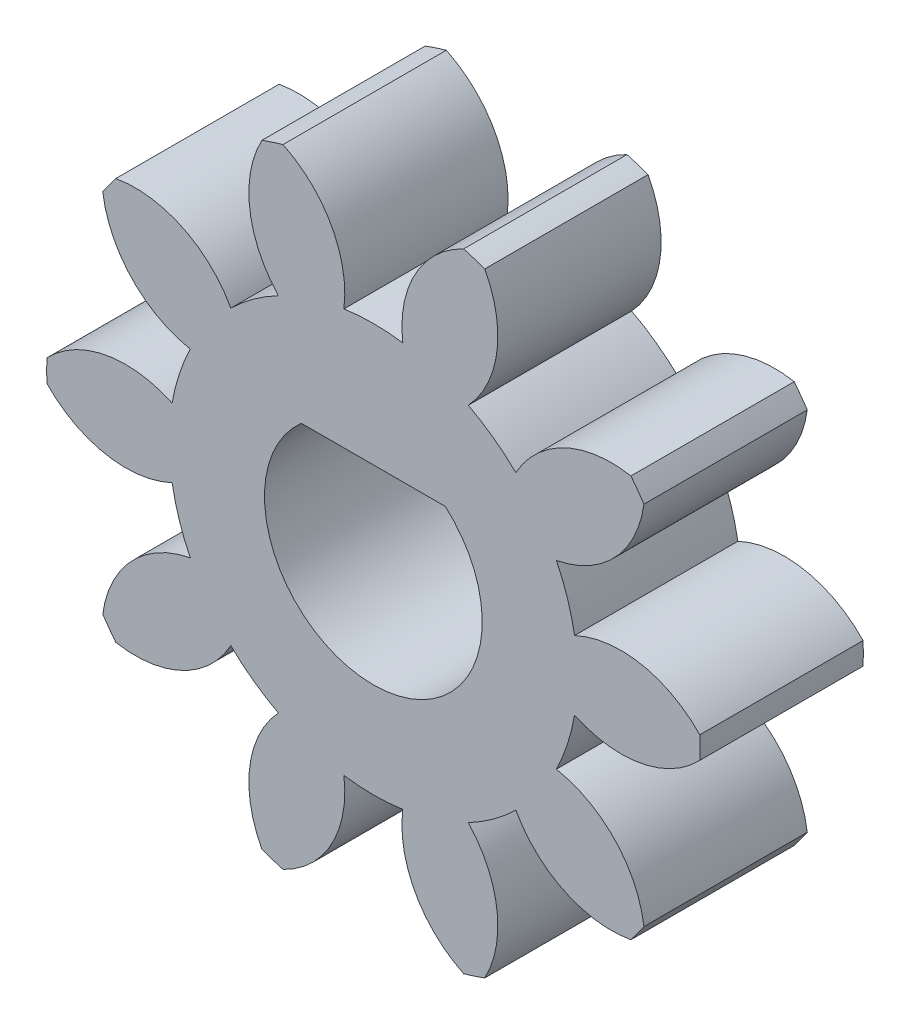
SolidWorks part; units mm, degrees
ref_plane "Front Plane" through (0, 0, 0) normal (0, 0, 1) x (1, 0, 0)
ref_plane "Top Plane" through (0, 0, 0) normal (0, 1, 0) x (1, 0, 0)
ref_plane "Right Plane" through (0, 0, 0) normal (1, 0, 0) x (0, 0, -1)
sketch "Sketch1" plane through (0, 0, 0) normal (0, 0, 1) x (1, 0, 0)
  circle A0 centre (0, 0) radius 6
  dimension "addendumDiameter" = 12
extrude "Boss-Extrude1" add sketch "Sketch1" along normal blind 3
sketch "Sketch2" plane through (0, 0, 3) normal (0, 0, 1) x (1, 0, 0)
  line L0 (0, 0) -> (0, 32.2263) construction
  line L1 (0, 0) -> (-6.6913, 20.5938) construction
  line L2 (-1.5259, 4.6963) -> (-0.7789, 4.939) construction
  circle A0 centre (0, 0) radius 3.75 construction
  circle A1 centre (0, 0) radius 4.6985 construction
  circle A2 centre (0, 0) radius 5 construction
  arc A3 (-1.6595, 5.7659) -> (-0.5404, 3.7109) centre (-2.5245, 3.9627) cw
  circle A4 centre (0, 0) radius 6 construction
  arc A5 (0.5404, 3.7109) -> (1.6595, 5.7659) centre (2.5245, 3.9627) cw
  arc A6 (-0.5404, 3.7109) -> (0.5404, 3.7109) centre (0, 0) cw
  arc A7 (-1.6595, 5.7659) -> (1.6595, 5.7659) centre (0, 0) cw
  dimension "dedendum circle" = 7.5
  dimension "base diameter" = 9.3969
  dimension "pitchDiameter" = 10
  dimension "D2" = 2
  dimension "D1" = 18
  dimension "D3" = 0.7854
extrude "Cut-Extrude1" cut sketch "Sketch2" against normal through all
pattern_circular "CirPattern1" count 10 over 360 about axis through (0, 0, 3) along (0, 0, 1) of "Cut-Extrude1"
sketch "Sketch4" [suppressed] plane through (0, 0, 3) normal (0, 0, 1) x (1, 0, 0)
  line L0 (0, 0) -> (0, 21.2521) construction
  line L3 (0, 0) -> (17.4265, 14.6226) construction
  line L4 (1.5677, 19.0606) -> (1.5677, 3.1277)
  line L5 (1.5677, 3.1277) -> (13.7196, 13.3244)
  line L6 (0, 0) -> (14.3062, 28.5426) construction
  arc A0 (13.7196, 13.3244) -> (1.5677, 19.0606) centre (0, 0) ccw
  arc A1 (8.9406, 18.5864) -> (7.83, 19.0809) centre (0, 0) ccw construction
  dimension "D3" = 3.4986
  dimension "D4" = 50
  dimension "D5" = 1.5
  dimension "D1" = 50
  dimension "D2" = 26.621
extrude "Cut-Extrude2" [suppressed] cut sketch "Sketch4" against normal through all contours L5 A0 L4
fillet "Fillet1" [suppressed] radius 0.75
pattern_circular "CirPattern2" [suppressed] count 6 over 360 of bodies 108
fillet "Fillet2" [suppressed] radius 0.75
pattern_circular "CirPattern3" [suppressed] count 6 over 360 of bodies 108
sketch "Sketch5" plane through (0, 0, 3) normal (0, 0, 1) x (1, 0, 0)
  line L0 (1.3229, 1.5) -> (-1.3229, 1.5)
  arc A0 (-1.3229, 1.5) -> (1.3229, 1.5) centre (0, 0) ccw
  dimension "D2" = 1.5
  dimension "D1" = 4
extrude "Cut-Extrude3" cut sketch "Sketch5" against normal through all
equation "\"module\"= 1.0"
equation "\"teeth\"= 10"
equation "\"pressureAngle\"= 20deg"
equation "\"gearThickness\"= 3"
equation "\"addendumFactor\"= 1"
equation "\"dedendumFactor\"= 1.25"
equation "\"pitch\"= 1 / \"module\""
equation "\"pitchDiameter\"= \"teeth\" / \"pitch\""
equation "\"addendum\"= \"addendumFactor\" / \"pitch\""
equation "\"dedendum\"= \"dedendumFactor\" / \"pitch\""
equation "\"D1@Boss-Extrude1\"=\"gearThickness\""
equation "\"addendumDiameter@Sketch1\"= \"pitchDiameter\" + 2 * \"addendum\""
equation "\"dedendum circle@Sketch2\"=\"pitchDiameter\" - 2 * \"dedendum\""
equation "\"base diameter@Sketch2\"=\"pitchDiameter\" * cos ( \"pressureAngle\" )"
equation "\"pitchDiameter@Sketch2\"=\"pitchDiameter\""
equation "\"D1@Sketch2\"=180/\"teeth\""
equation "\"D2@Sketch2\"=\"pitchDiameter\"/5"
equation "\"D3@Sketch2\"=PI/2/\"pitch\"/2"
equation "\"D1@CirPattern1\"=\"teeth\""
